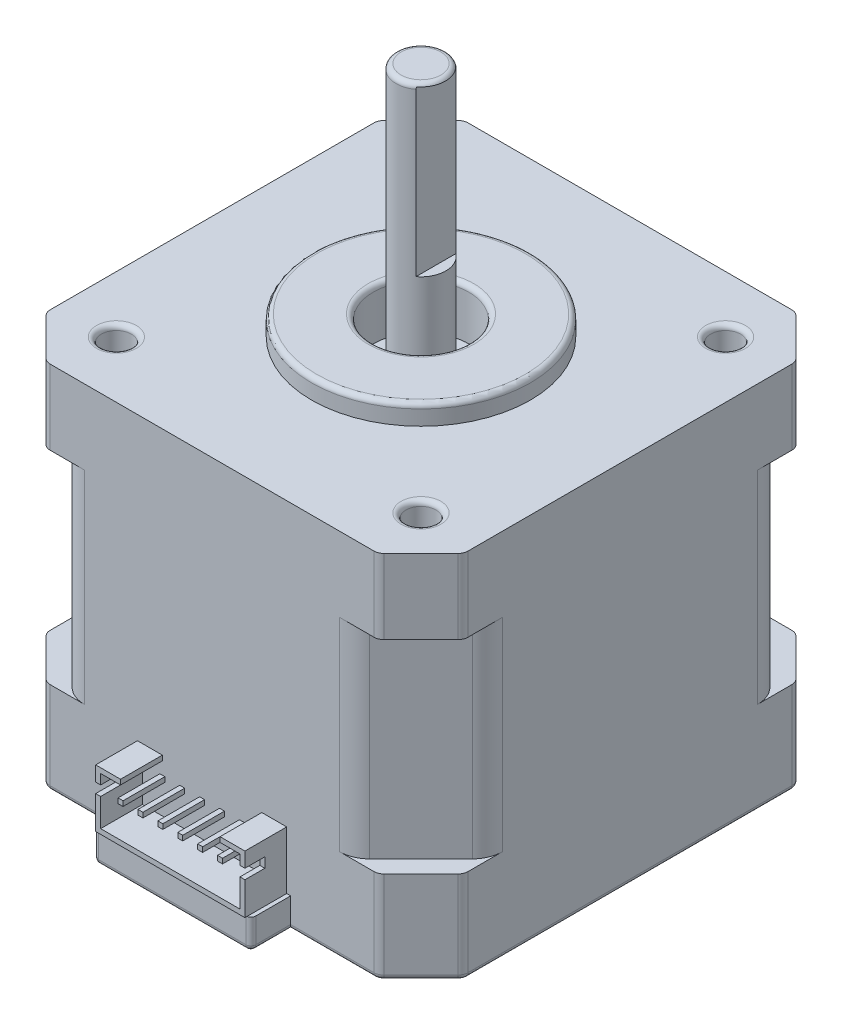
SolidWorks part; units mm, degrees
material "1060 Alloy"
ref_plane "Front Plane" through (0, 0, 0) normal (0, 0, 1) x (1, 0, 0)
ref_plane "Top Plane" through (0, 0, 0) normal (0, 1, 0) x (1, 0, 0)
ref_plane "Right Plane" through (0, 0, 0) normal (1, 0, 0) x (0, 0, -1)
sketch "Sketch1" plane through (0, 0, 0) normal (0, 1, 0) x (1, 0, 0)
  line L0 (0, -1000) -> (0, 49000) construction
  line L1 (-16.6866, -21) -> (16.6866, -21)
  line L2 (-21, 16.6866) -> (-21, -16.6866)
  line L3 (-16.6866, 21) -> (16.6866, 21)
  line L4 (21, -16.6866) -> (21, 16.6866)
  line L5 (-1000, 0) -> (49000, 0) construction
  line L6 (0, 0) -> (35355.3391, 35355.3391) construction
  line L7 (16.6866, 21) -> (21, 16.6866)
  line L8 (21, -16.6866) -> (16.6866, -21)
  line L9 (-16.6866, -21) -> (-21, -16.6866)
  line L10 (-21, 16.6866) -> (-16.6866, 21)
  point P0 (0, 0)
  point P25 (0, 0)
  dimension "D1" = 45
  dimension "D2" = 42
  dimension "D4" = 6.1
  dimension "D3" = 6.1
  dimension "D5" = 4
extrude "Boss-Extrude1" add sketch "Sketch1" along normal blind 37.2
sketch "Sketch2" plane through (0, 37.2, 0) normal (0, 1, 0) x (1, 0, 0)
  circle A0 centre (0, 0) radius 11
  dimension "D1" = 22
extrude "Boss-Extrude2" add sketch "Sketch2" along normal blind 2
sketch "Sketch3" plane through (0, 39.2, 0) normal (0, 1, 0) x (1, 0, 0)
  circle A0 centre (0, 0) radius 2.5
extrude "Boss-Extrude3" add sketch "Sketch3" along normal blind 21.8
sketch "Sketch5" plane through (0, 37.2, 0) normal (0, 1, 0) x (1, 0, 0)
  line L0 (-1000, 0) -> (49000, 0) construction
  line L1 (0, -1000) -> (0, 49000) construction
  line L3 (21, 16.6866) -> (16.6866, 21) construction
  line L4 (-21, 16.6866) -> (-21, -16.6866) construction
  line L6 (0, 0) -> (35355.3391, 35355.3391) construction
  line L7 (0, 0) -> (15.3078, 15.3078) construction
  circle A1 centre (15.3078, 15.3078) radius 1.5
  circle A2 centre (15.3078, -15.3078) radius 1.5
  circle A3 centre (-15.3078, -15.3078) radius 1.5
  circle A4 centre (-15.3078, 15.3078) radius 1.5
  dimension "D1" = 3
  dimension "D2" = 5
  dimension "D3" = 45
  dimension "D4" = 4
  dimension "D6" = 5.6922
  dimension "D5" = 21.6485
extrude "Cut-Extrude1" cut sketch "Sketch5" against normal blind 4.5
sketch "Sketch7" plane through (0, 0, 0) normal (0, -1, 0) x (1, 0, 0)
  line L0 (0, -1000) -> (0, 49000) construction
  line L1 (-1000, 0) -> (49000, 0) construction
  line L2 (0, 0) -> (15.2371, 15.2371) construction
  line L3 (21, 16.6866) -> (21, -16.6866) construction
  line L4 (16.6866, 21) -> (21, 16.6866) construction
  line L5 (0, 0) -> (35355.3391, 35355.3391) construction
  circle A0 centre (15.2371, -15.2371) radius 3.1
  circle A1 centre (-15.2371, -15.2371) radius 3.1
  circle A2 centre (-15.2371, 15.2371) radius 3.1
  circle A5 centre (15.2371, 15.2371) radius 3.1
  dimension "D2" = 6.2
  dimension "D4" = 5.1
  dimension "D1" = 5.1
  dimension "D3" = 45
  dimension "D5" = 4
  dimension "D6" = 21.5485
  dimension "D7" = 5.7629
extrude "Cut-Extrude2" cut sketch "Sketch7" against normal blind 5
ref_plane "Plane1" through (0, 9.3, 0) normal (0, 1, 0) x (1, 0, 0)
sketch "Sketch9" plane through (0, 9.3, 0) normal (0, 1, 0) x (1, 0, 0)
  line L0 (14.0704, 21) -> (21, 14.0704)
  line L1 (16.6866, 21) -> (-16.6866, 21) construction
  line L2 (0, 0) -> (35355.3391, 35355.3391) construction
  line L3 (21, 16.6866) -> (16.6866, 21) construction
  line L4 (14.0704, 21) -> (16.6866, 21)
  line L5 (16.6866, 21) -> (21, 16.6866)
  line L6 (21, 16.6866) -> (21, 14.0704)
  line L7 (21, -14.0704) -> (14.0704, -21)
  line L8 (21, -14.0704) -> (21, -16.6866)
  line L9 (21, -16.6866) -> (16.6866, -21)
  line L10 (16.6866, -21) -> (14.0704, -21)
  line L11 (-14.0704, -21) -> (-21, -14.0704)
  line L12 (-14.0704, -21) -> (-16.6866, -21)
  line L13 (-16.6866, -21) -> (-21, -16.6866)
  line L14 (-21, -16.6866) -> (-21, -14.0704)
  line L15 (-21, 14.0704) -> (-14.0704, 21)
  line L16 (-21, 14.0704) -> (-21, 16.6866)
  line L17 (-21, 16.6866) -> (-16.6866, 21)
  line L18 (-16.6866, 21) -> (-14.0704, 21)
  line L19 (0, 0) -> (21, 14.0704) construction
  point P9 (18.8433, 18.8433)
  dimension "D1" = 9.8
  dimension "D2" = 4
  dimension "D3" = 25.278
  dimension "D4" = 14.0704
extrude "Cut-Extrude3" cut sketch "Sketch9" along normal blind 20.4
sketch "Sketch11" plane through (0, 0, 0) normal (0, -1, 0) x (1, 0, 0)
  circle A0 centre (0, 0) radius 4.6
  dimension "D1" = 9.2
extrude "Cut-Extrude4" cut sketch "Sketch11" against normal blind 4.3
sketch "Sketch12" plane through (0, 4.3, 0) normal (0, -1, 0) x (1, 0, 0)
  circle A0 centre (0, 0) radius 2.4
  dimension "D1" = 4.8
extrude "Boss-Extrude4" add sketch "Sketch12" along normal blind 2
ref_plane "Plane2" through (0, 44.2, 0) normal (0, 1, 0) x (1, 0, 0)
sketch "Sketch13" plane through (0, 44.2, 0) normal (0, 1, 0) x (1, 0, 0)
  line L0 (1.5, -2) -> (1.5, 2)
  circle A0 centre (0, 0) radius 2.5 construction
  arc A1 (1.5, -2) -> (1.5, 2) centre (0, 0) ccw
  dimension "D1" = 1.5
extrude "Cut-Extrude5" cut sketch "Sketch13" along normal blind 16.5
sketch "Sketch15" plane through (0, 0, 21) normal (0, 0, 1) x (1, 0, 0)
  line L0 (0, -1000) -> (0, 49000) construction
  line L1 (-16.6866, 0) -> (16.6866, 0) construction
  line L2 (-7.9, 0) -> (7.9, 0)
  line L3 (-7.9, 0) -> (-7.9, 3)
  line L4 (-7.9, 3) -> (7.9, 3)
  line L5 (7.9, 0) -> (7.9, 3)
  dimension "D1" = 3
  dimension "D2" = 15.8
extrude "Boss-Extrude6" add sketch "Sketch15" along normal blind 4
sketch "Sketch16" plane through (0, 0, 21) normal (0, 0, 1) x (1, 0, 0)
  line L0 (0, -1000) -> (0, 49000) construction
  line L1 (7.9, 3) -> (-7.9, 3) construction
  line L2 (-7.5, 3) -> (7.5, 3)
  line L3 (-7.5, 3) -> (-7.5, 8.8)
  line L4 (-7.5, 8.8) -> (7.5, 8.8)
  line L5 (7.5, 3) -> (7.5, 8.8)
  dimension "D1" = 5.8
  dimension "D2" = 15
extrude "Boss-Extrude7" add sketch "Sketch16" along normal blind 4.2
sketch "Sketch18" plane through (0, 0, 25.2) normal (0, 0, 1) x (1, 0, 0)
  line L0 (7, 8.3) -> (7, 3.5)
  line L1 (-7, 8.3) -> (-5, 8.3)
  line L2 (-7, 8.3) -> (-7, 3.5)
  line L3 (-7, 3.5) -> (7, 3.5)
  line L4 (7, 8.3) -> (5, 8.3)
  line L5 (-7.5, 8.8) -> (-7.5, 3) construction
  line L6 (-7.5, 3) -> (7.5, 3) construction
  line L7 (0, -1000) -> (0, 49000) construction
  line L8 (-5, 8.3) -> (-5, 8.8)
  line L9 (7.5, 8.8) -> (-7.5, 8.8) construction
  line L10 (-5, 8.8) -> (5, 8.8)
  line L11 (5, 8.3) -> (5, 8.8)
  line L12 (7.5, 8.8) -> (-7.5, 8.8) construction
  point P6 (-7.5, 5.9)
  point P19 (0, 8.8)
  dimension "D1" = 0.5
  dimension "D2" = 0.5
  dimension "D3" = 2
  dimension "D4" = 0.5
  dimension "D5" = 0.5
extrude "Cut-Extrude6" cut sketch "Sketch18" against normal up to surface (4.2 mm away) contours L10 L11 L4 L0 L3 L2 L1 L8 up to face at (-0.4393, 13, 21)
sketch "Sketch19" plane through (0, 0, 25.2) normal (0, 0, 1) x (1, 0, 0)
  line L0 (-1002.394, 6.8) -> (48997.606, 6.8) construction
  line L1 (-7, 8.3) -> (-7, 3.5) construction
  line L2 (-7, 8.3) -> (-5, 8.3) construction
  line L4 (-7, 7.3) -> (-7.5, 7.3)
  line L5 (-7, 7.3) -> (-7, 6.3)
  line L6 (-7, 6.3) -> (-7.5, 6.3)
  line L7 (-7.5, 7.3) -> (-7.5, 6.3)
  line L9 (-7.5, 8.8) -> (-7.5, 3) construction
  line L10 (0, -1000) -> (0, 49000) construction
  line L11 (7.5, 7.3) -> (7.5, 6.3)
  line L12 (7, 6.3) -> (7.5, 6.3)
  line L13 (7, 7.3) -> (7, 6.3)
  line L14 (7, 7.3) -> (7.5, 7.3)
  dimension "D1" = 1.5
  dimension "D2" = 1
extrude "Cut-Extrude8" cut sketch "Sketch19" against normal blind 2
sketch "Sketch20" plane through (0, 0, 21) normal (0, 0, 1) x (1, 0, 0)
  line L0 (-1007.6, 6.8) -> (48992.4, 6.8) construction
  line L1 (-7.5, 7.3) -> (-7.5, 6.3) construction
  line L3 (-3.25, 6.55) -> (-3.25, 7.05)
  line L4 (-5.25, 6.55) -> (-4.75, 6.55)
  line L5 (-5.25, 6.55) -> (-5.25, 7.05)
  line L6 (-5.25, 7.05) -> (-4.75, 7.05)
  line L7 (-4.75, 6.55) -> (-4.75, 7.05)
  line L8 (-5.25, 6.55) -> (-4.75, 7.05) construction
  line L9 (-5.25, 7.05) -> (-4.75, 6.55) construction
  line L10 (-3.25, 7.05) -> (-2.75, 7.05)
  line L11 (-2.75, 6.55) -> (-2.75, 7.05)
  line L12 (-3.25, 6.55) -> (-2.75, 6.55)
  line L13 (-1.25, 6.55) -> (-1.25, 7.05)
  line L14 (-1.25, 7.05) -> (-0.75, 7.05)
  line L15 (-0.75, 6.55) -> (-0.75, 7.05)
  line L16 (-1.25, 6.55) -> (-0.75, 6.55)
  line L17 (0.75, 6.55) -> (0.75, 7.05)
  line L18 (0.75, 7.05) -> (1.25, 7.05)
  line L19 (1.25, 6.55) -> (1.25, 7.05)
  line L20 (0.75, 6.55) -> (1.25, 6.55)
  line L21 (2.75, 6.55) -> (2.75, 7.05)
  line L22 (2.75, 7.05) -> (3.25, 7.05)
  line L23 (3.25, 6.55) -> (3.25, 7.05)
  line L24 (2.75, 6.55) -> (3.25, 6.55)
  line L25 (4.75, 6.55) -> (4.75, 7.05)
  line L26 (4.75, 7.05) -> (5.25, 7.05)
  line L27 (5.25, 6.55) -> (5.25, 7.05)
  line L28 (4.75, 6.55) -> (5.25, 6.55)
  line L29 (7.5, 3) -> (7.5, 8.8) construction
  line L30 (7.5, 8.8) -> (5, 8.8) construction
  line L32 (-7, 6.3) -> (-7, 7.3) construction
  line L33 (7, 8.3) -> (7, 3.5) construction
  circle A0 centre (-5, 6.8) radius 0.25 construction
  point P5 (-7.5, 6.8)
  dimension "D1" = 0.5
  dimension "D2" = 2
  dimension "D3" = 0.5
  dimension "D4" = 6
  dimension "D5" = 1.75
  dimension "D6" = 0.25
extrude "Boss-Extrude8" add sketch "Sketch20" along normal up to surface (4.2 mm away) up to face at (0, 4.775, 25.2)
sketch "Sketch21" plane through (0, 5, 0) normal (0, -1, 0) x (1, 0, 0)
  line L0 (-15.2371, -985.5578) -> (-15.2371, 49014.4422) construction
  line L1 (-1015.2371, 15.2371) -> (48984.7629, 15.2371) construction
  line L2 (-15.7371, 16.9871) -> (-15.7371, 16.7371)
  line L3 (-16.7371, 15.7371) -> (-16.9871, 15.7371)
  line L4 (-16.9871, 15.7371) -> (-16.9871, 14.7371)
  line L5 (-16.9871, 14.7371) -> (-16.7371, 14.7371)
  line L6 (-15.7371, 13.7371) -> (-15.7371, 13.4871)
  line L7 (-15.7371, 13.4871) -> (-14.7371, 13.4871)
  line L8 (-15.7371, 16.9871) -> (-14.7371, 16.9871)
  line L9 (-14.7371, 16.9871) -> (-14.7371, 16.7371)
  line L10 (-13.7371, 15.7371) -> (-13.4871, 15.7371)
  line L11 (-13.4871, 15.7371) -> (-13.4871, 14.7371)
  line L12 (-13.4871, 14.7371) -> (-13.7371, 14.7371)
  line L13 (-14.7371, 13.7371) -> (-14.7371, 13.4871)
  circle A0 centre (-15.2371, 15.2371) radius 2.5
  arc A1 (-16.7371, 14.7371) -> (-15.7371, 13.7371) centre (-16.7371, 13.7371) cw
  arc A2 (-13.7371, 14.7371) -> (-14.7371, 13.7371) centre (-13.7371, 13.7371) ccw
  arc A3 (-14.7371, 16.7371) -> (-13.7371, 15.7371) centre (-13.7371, 16.7371) ccw
  arc A4 (-15.7371, 16.7371) -> (-16.7371, 15.7371) centre (-16.7371, 16.7371) cw
  point P21 (-15.7371, 14.7371)
  dimension "D1" = 5
  dimension "D6" = 1
  dimension "D2" = 1
  dimension "D3" = 1
  dimension "D4" = 3.5
  dimension "D5" = 3.5
extrude "Boss-Extrude9" add sketch "Sketch21" along normal blind 4.5
pattern_circular "CirPattern1" count 4 over 360 about axis through (0, 2.3, 0) along (0, -1, 0) of "Boss-Extrude9"
sketch "Sketch22" plane through (0, 39.2, 0) normal (0, 1, 0) x (1, 0, 0)
  circle A0 centre (0, 0) radius 4.8
  circle A1 centre (0, 0) radius 2.5
  circle A2 centre (0, 0) radius 2.5 construction
  dimension "D1" = 9.6
extrude "Cut-Extrude12" cut sketch "Sketch22" against normal blind 5
fillet "Fillet1" radius 1 16 edges at (-16.6866, 33.45, -21) (16.6866, 33.45, -21) (21, 33.45, -16.6866) (-16.6866, 33.45, 21) (-21, 33.45, 16.6866) (-21, 33.45, -16.6866) (16.6866, 33.45, 21) (-21, 4.65, -16.6866) (-21, 4.65, 16.6866) (-16.6866, 4.65, 21) (21, 4.65, 16.6866) (21, 4.65, -16.6866) (16.6866, 4.65, -21) (-16.6866, 4.65, -21) (16.6866, 4.65, 21) (21, 33.45, 16.6866)
fillet "Fillet2" radius 3 8 edges at (-14.0704, 19.5, 21) (-21, 19.5, 14.0704) (-21, 19.5, -14.0704) (-14.0704, 19.5, -21) (14.0704, 19.5, -21) (21, 19.5, -14.0704) (21, 19.5, 14.0704) (14.0704, 19.5, 21)
fillet "Fillet3" radius 0.5 5 edges at (15.3078, 37.2, -13.8078) (-15.3078, 37.2, -13.8078) (15.3078, 37.2, 16.8078) (-15.3078, 37.2, 16.8078) (0, 39.2, 11)
fillet "Fillet4" radius 0.5 5 edges at (15.2371, 0, -18.3371) (-15.2371, 0, -18.3371) (-15.2371, 0, 12.1371) (15.2371, 0, 12.1371) (0, 0, -4.6)
fillet "Fillet5" radius 0.5 1 edges at (0, 61, 2.5)
fillet "Fillet7" radius 0.5 22 edges at (-20.9239, 0, 16.6551) (-18.8433, 0, 18.8433) (-16.6551, 0, 20.9239) (0, 0, 25) (16.6551, 0, 20.9239) (18.8433, 0, 18.8433) (20.9239, 0, 16.6551) (20.9239, 0, -16.6551) (18.8433, 0, -18.8433) (16.6551, 0, -20.9239) (0, 0, -21) (-16.6551, 0, -20.9239) (-18.8433, 0, -18.8433) (-20.9239, 0, -16.6551) (-21, 0, 0) (21, 0, 0) (7.9, 1.5, 25) (-7.9, 1.5, 25)
fillet "Fillet8" radius 0.5 1 edges at (0, 39.2, 4.8)
